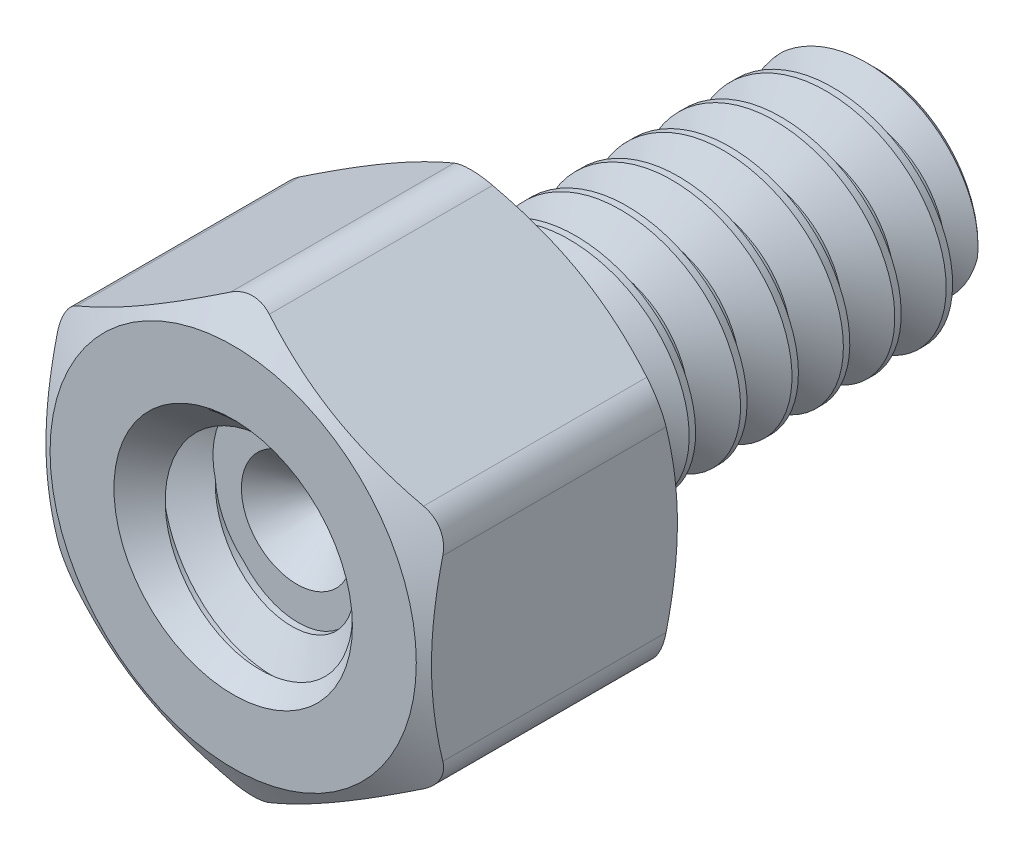
SolidWorks part; units mm, degrees
ref_plane "Front Plane" through (0, 0, 0) normal (0, 0, 1) x (1, 0, 0)
ref_plane "Top Plane" through (0, 0, 0) normal (0, 1, 0) x (1, 0, 0)
ref_plane "Right Plane" through (0, 0, 0) normal (1, 0, 0) x (0, 0, -1)
sketch "Sketch1" plane through (0, 0, 0) normal (0, 0, 1) x (1, 0, 0)
  line L1 (2.3813, 1.3748) -> (0, 2.7496)
  line L2 (0, 2.7496) -> (-2.3812, 1.3748)
  line L3 (-2.3812, 1.3748) -> (-2.3812, -1.3748)
  line L4 (-2.3812, -1.3748) -> (0, -2.7496)
  line L5 (0, -2.7496) -> (2.3813, -1.3748)
  line L6 (2.3813, -1.3748) -> (2.3813, 1.3748)
  circle A0 centre (0, 0) radius 2.3812 construction
  point P10 (0, -2.3812)
  dimension "Hex Size" = 4.7625
sketch "Sketch2" plane through (0, 0, 0) normal (1, 0, 0) x (0, 0, -1)
  line L0 (4.7625, 0) -> (-3.175, 0) construction
  line L2 (0, 1.4224) -> (0, -1.4224) construction
  line L3 (-2.3876, 1.4224) -> (-2.3876, -1.4224) construction
  line L4 (-3.7703, 1.4911) -> (-3.4528, 0.9412) construction
  line L5 (-3.4528, 0.9412) -> (-3.1353, 1.4911) construction
  line L6 (-3.1353, 1.4911) -> (-3.7703, 1.4911) construction
  line L7 (-3.7306, 1.4224) -> (-3.175, 1.4224) construction
  line L8 (-3.4925, 1.01) -> (-3.4131, 1.01) construction
  line L9 (-3.4528, 1.01) -> (-3.4528, 0.9412) construction
  line L10 (-3.4528, 1.4224) -> (-3.4528, 1.4911) construction
  line L11 (4.7228, 1.4911) -> (5.3578, 1.4911) construction
  line L12 (5.3578, 1.4911) -> (5.0403, 0.9412) construction
  line L13 (5.0403, 0.9412) -> (4.7228, 1.4911) construction
  line L14 (4.7625, 1.4224) -> (5.3181, 1.4224) construction
  line L15 (5.0006, 1.01) -> (5.08, 1.01) construction
  line L16 (5.0403, 1.01) -> (5.0403, 0.9412) construction
  line L17 (5.0403, 1.4224) -> (5.0403, 1.4911) construction
  line L18 (0, 2.7496) -> (-3.175, 2.7496) construction
  point P6 (0, 0)
  point P9 (-2.3876, 0)
  dimension "Length" = 3.175
sketch "Sketch3" plane through (0, 0, 0) normal (1, 0, 0) x (0, 0, -1)
  line L0 (-2.3876, 0) -> (4.7625, 0)
  line L1 (-2.3876, 1.4224) -> (-2.3876, -1.4224) construction
  line L2 (4.7625, 0) -> (4.7625, 1.2636)
  line L3 (4.7625, 1.2636) -> (4.6038, 1.4224)
  line L4 (4.6038, 1.4224) -> (0.8096, 1.4224)
  line L5 (0.8096, 1.4224) -> (0.5715, 1.01)
  line L6 (-2.3876, 0) -> (-2.3876, 1.2636)
  line L7 (-2.3876, 1.2636) -> (-2.5464, 1.4224)
  line L8 (-2.5464, 1.4224) -> (-3.0162, 1.4224)
  line L9 (-3.0162, 1.4224) -> (-3.175, 1.5811)
  line L10 (4.6038, 0) -> (4.6038, -1.4224) construction
  line L11 (-3.175, 1.5811) -> (-3.175, 2.3812)
  line L12 (-3.175, 2.3812) -> (0, 2.3812)
  line L14 (0.5715, 1.01) -> (0.1587, 1.01)
  line L15 (0, 1.1687) -> (0, 2.3812)
  arc A0 (0, 1.1687) -> (0.1587, 1.01) centre (0.1587, 1.1687) ccw
  point P5 (-3.175, -2.3812)
  point P8 (-1.5875, -1.4224)
  point P9 (3.175, -1.4224)
  point P27 (0, 1.01)
  dimension "D4" = 0.1588
  dimension "D2" = 0.1588
  dimension "D1" = 45
  dimension "D6" = 1.5875
  dimension "D7" = 60
  dimension "D3" = 1.5875
  dimension "D5" = 0.5715
revolve "Revolve1" add sketch "Sketch3" angle 360 about L0 region at (0, 0.9797, -0.549)
sketch "Sketch4" plane through (0, 0, 3.175) normal (0, 0, 1) x (1, 0, 0)
  line L0 (0, 2.3812) -> (0, 1.4224) construction
  line L1 (-2.3812, 1.3748) -> (-2.3812, -1.3748)
  line L2 (-2.3812, -1.3748) -> (0, -2.7496)
  line L3 (0, -2.7496) -> (2.3812, -1.3748)
  line L4 (2.3812, -1.3748) -> (2.3812, 1.3748)
  line L5 (2.3812, 1.3748) -> (0, 2.7496)
  line L6 (0, 2.7496) -> (-2.3812, 1.3748)
  circle A0 centre (0, 0) radius 2.3812 construction
  circle A1 centre (0, 0) radius 1.9018
  circle A2 centre (0, 0) radius 2.3812 construction
  point P16 (0, 1.9018)
extrude "Boss-Extrude1" add sketch "Sketch4" against normal up to surface (3.175 mm away) up to face at (0, 2.3812, 0)
sketch "Sketch5" plane through (0, 0, 3.175) normal (0, 0, 1) x (1, 0, 0)
  line L0 (-0.8159, 1.1652) -> (0.8159, -1.1652) construction
  line L1 (0, 1.4224) -> (0, -1.4224) construction
  line L3 (0, -4.9059) -> (0, 4.9059) construction
  circle A0 centre (0, 0) radius 2.2622
  point P11 (0.8159, -1.1652)
  dimension "D1" = 4.5244
  dimension "D2" = 35
extrude "Cut-Extrude1" cut sketch "Sketch5" against normal through all draft 60 flip side to cut
sketch "Sketch6" plane through (0, 0, 0) normal (0, 0, -1) x (-1, 0, 0)
  circle A0 centre (0, 0) radius 2.2622
  circle A1 centre (0, 0) radius 2.2622 construction
extrude "Cut-Extrude2" cut sketch "Sketch6" against normal through all draft 60 flip side to cut
fillet "Fillet1" radius 0.4763 6 edges at (0, 2.7496, 1.5875) (-2.3812, -1.3748, 1.5875) (0, -2.7496, 1.5875) (2.3812, -1.3748, 1.5875) (2.3812, 1.3748, 1.5875) (-2.3812, 1.3748, 1.5875)
sketch "Drawing1" plane through (0, 0, 0) normal (1, 0, 0) x (0, 0, -1)
  line L0 (-3.175, 1.4224) -> (-2.3876, 1.4224) construction
  line L1 (-2.3876, 1.4224) -> (-2.3876, -1.4224) construction
  line L2 (-2.3876, -1.4224) -> (-3.175, -1.4224) construction
sketch "Sketch7" plane through (0, 0, 0) normal (-1, 0, 0) x (0, 0, 1)
  line L0 (-5.0006, 1.01) -> (-5.08, 1.01)
  line L1 (-5.08, 1.01) -> (-5.338, 1.4568)
  line L2 (-5.3578, 1.4911) -> (-5.0403, 0.9412) construction
  line L3 (-5.338, 1.4568) -> (-4.7427, 1.4568)
  line L4 (-5.0403, 0.9412) -> (-4.7228, 1.4911) construction
  line L5 (-4.7427, 1.4568) -> (-5.0006, 1.01)
  line L6 (-5.0403, 1.4224) -> (-5.0403, 1.4911) construction
  point P12 (-5.0403, 1.4568)
sketch "Sketch8" plane through (0, 0, -4.7625) normal (0, 0, -1) x (-1, 0, 0)
  circle A0 centre (0, 0) radius 1.4224
curve "Helix/Spiral1" pitch 0.635 height 4.6196 radius 1.4224 centre (0, 0, -4.7625) axis (0, 0, 1) start towards (0, 1, 0)
sweep "Cut-Sweep1" cut profiles "Sketch7" path "Helix/Spiral1" align with end faces yes
sketch "Sketch9" plane through (0, 0, 2.3876) normal (0, 0, 1) x (1, 0, 0)
  circle A0 centre (0, 0) radius 1.5811
extrude "Boss-Extrude2" add sketch "Sketch9" along normal up to surface (0.7874 mm away) up to face at (0, 1.5811, 3.175)
sketch "Sketch10" plane through (0, 0, 0) normal (1, 0, 0) x (0, 0, -1)
  line L0 (4.7625, 0) -> (-3.175, 0) construction
  line L1 (-2.3876, 1.4224) -> (-3.175, 1.4224)
  line L2 (-2.3876, 1.4224) -> (-2.3876, 0)
  line L3 (-2.3876, 0) -> (-3.175, 0)
  line L4 (-3.175, 1.4224) -> (-3.175, 0)
revolve "Revolve2" add sketch "Sketch10" angle 360 about L0
sketch "Sketch11" plane through (0, 0, 3.175) normal (0, 0, 1) x (1, 0, 0)
  circle A0 centre (0, 0) radius 1.4224
  circle A1 centre (0, 0) radius 1.4224 construction
sketch "Sketch12" plane through (0, 0, 0) normal (1, 0, 0) x (0, 0, -1)
  line L0 (-3.4925, 1.01) -> (-3.4131, 1.01)
  line L1 (-3.4131, 1.01) -> (-3.1552, 1.4568)
  line L2 (-3.4528, 0.9412) -> (-3.1353, 1.4911) construction
  line L3 (-3.1552, 1.4568) -> (-3.7505, 1.4568)
  line L4 (-3.7703, 1.4911) -> (-3.4528, 0.9412) construction
  line L5 (-3.7505, 1.4568) -> (-3.4925, 1.01)
  line L6 (-3.4528, 1.4224) -> (-3.4528, 1.4911) construction
  point P12 (-3.4528, 1.4568)
curve "Helix/Spiral2" pitch 0.635 height 1.4224 radius 1.4224 centre (0, 0, 3.175) axis (0, 0, -1) start towards (0, 1, 0)
sweep "Cut-Sweep2" cut profiles "Sketch12" path "Helix/Spiral2" align with end faces yes
combine bodies "Combine1" operation type subtract main body 113 bodies to subtract 114
sketch "Sketch13" plane through (0, 0, 3.175) normal (0, 0, 1) x (1, 0, 0)
  circle A0 centre (0, 0) radius 1.4732
  dimension "D1" = 0.0508
extrude "Cut-Extrude3" cut sketch "Sketch13" against normal through all draft 45
equation "\"Thread Pitch (B)/8@Sketch2\"=\"Thread Pitch (B)@Sketch2\"/8"
equation "\"Thread Pitch (A)/8@Sketch2\"=\"Thread Pitch (A)@Sketch2\"/8"
equation "\"D1@Sketch5\" = \"Hex Size@Sketch1\" * .95"
equation "\"D1@Fillet1\" = \"Hex Size@Sketch1\" * .1"
equation "\"D2@Sketch3\" = \"Thread Pitch (A)@Sketch2\" * .25"
equation "\"D4@Sketch3\" = \"D2@Sketch3\""
equation "\"D6@Sketch3\" = \"Thread Pitch (A)@Sketch2\" * 2.5"
equation "\"D3@Helix/Spiral1\" = \"Thread Length (A)@Sketch2\" - \"D5@Sketch3\" * .25"
equation "\"D4@Helix/Spiral1\" = \"Thread Pitch (A)@Sketch2\""
equation "\"D3@Sketch3\" = \"Thread Pitch (B)@Sketch2\" * 2.5"
equation "\"D5@Sketch3\" = \"Thread Length (A)@Sketch2\" * .12"
equation "\"D3@Helix/Spiral2\" = \"Minimum Thread Length (B)@Sketch2\" + \"Thread Pitch (B)@Sketch2\""
equation "\"D4@Helix/Spiral2\" = \"Thread Pitch (B)@Sketch2\""
